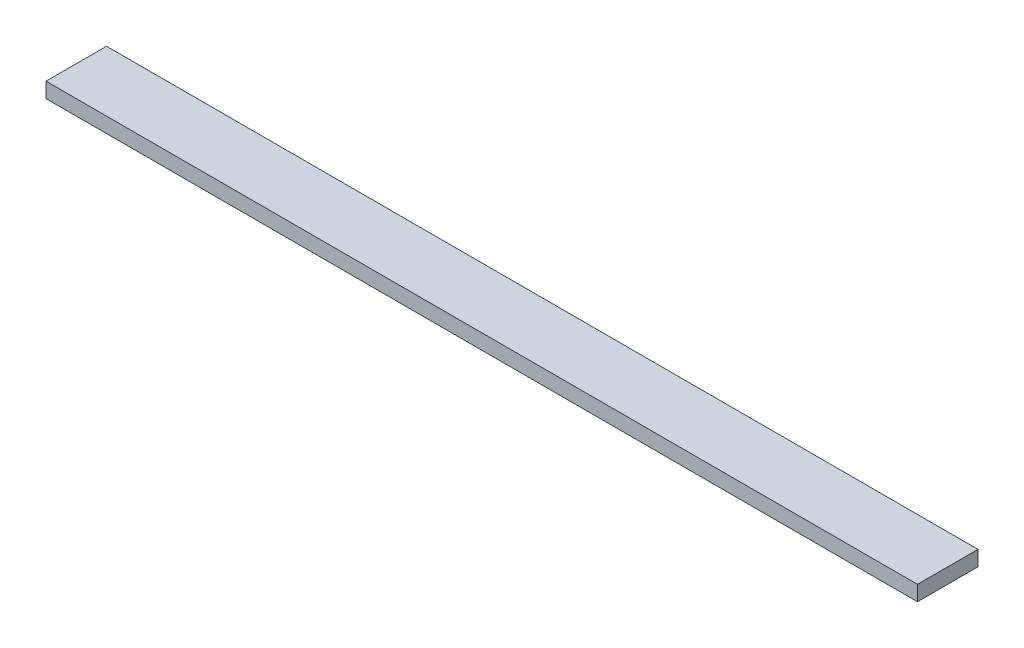
SolidWorks part; units mm, degrees
ref_plane "Front Plane" through (0, 0, 0) normal (0, 0, 1) x (1, 0, 0)
ref_plane "Top Plane" through (0, 0, 0) normal (0, 1, 0) x (1, 0, 0)
ref_plane "Right Plane" through (0, 0, 0) normal (1, 0, 0) x (0, 0, -1)
sketch "Sketch1" plane through (0, 0, 0) normal (0, 1, 0) x (1, 0, 0)
  line L1 (0, 0) -> (914.4, 0)
  line L2 (0, 0) -> (0, 63.5)
  line L3 (0, 63.5) -> (914.4, 63.5)
  line L4 (914.4, 0) -> (914.4, 63.5)
  dimension "D1" = 63.5
  dimension "D2" = 914.4
extrude "Boss-Extrude1" add sketch "Sketch1" along normal blind 15.875
